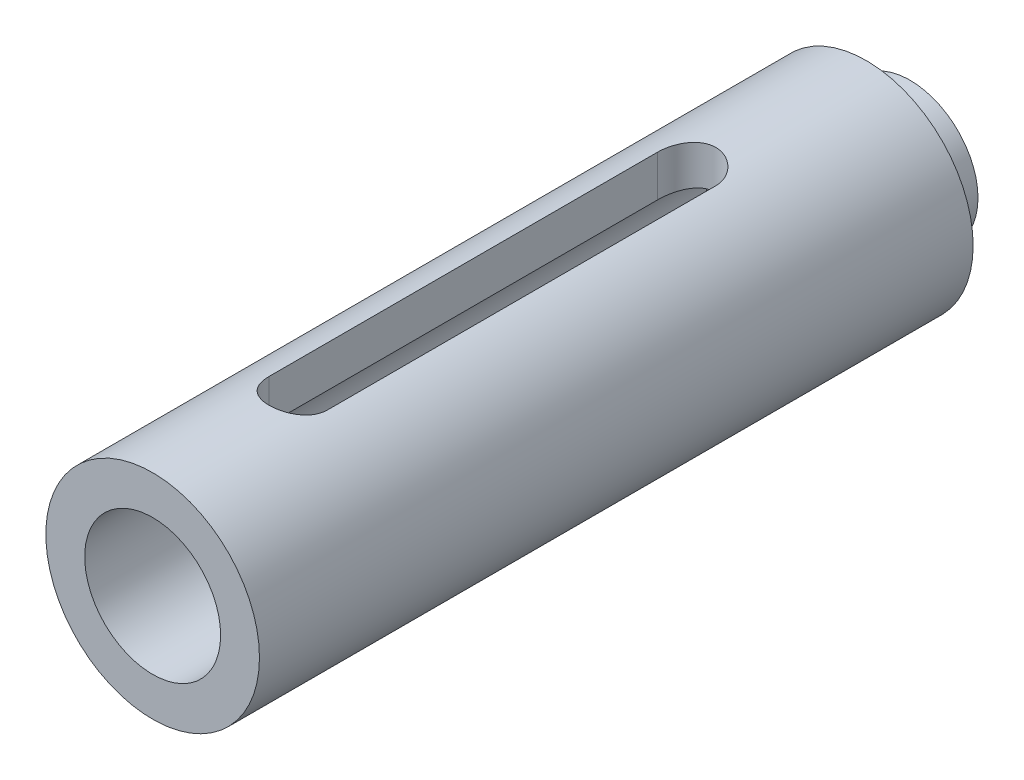
SolidWorks part; units mm, degrees
material "Zinc AC41A Alloy, As Cast"
ref_plane "Plan de face" through (0, 0, 0) normal (0, 0, 1) x (1, 0, 0)
ref_plane "Plan de dessus" through (0, 0, 0) normal (0, 1, 0) x (1, 0, 0)
ref_plane "Plan de droite" through (0, 0, 0) normal (1, 0, 0) x (0, 0, -1)
sketch "Sketch1" plane through (0, 0, 0) normal (0, 0, 1) x (1, 0, 0)
  circle A0 centre (0, 0) radius 3.5
  dimension "D1" = 7
extrude "Boss-Extrude1" add sketch "Sketch1" along normal blind 2.25
sketch "Sketch2" plane through (0, 0, 2.25) normal (0, 0, 1) x (1, 0, 0)
  circle A0 centre (0, 0) radius 5.5
  dimension "D1" = 11
extrude "Boss-Extrude2" add sketch "Sketch2" along normal blind 36.75
sketch "Sketch3" plane through (0, 0, 39) normal (0, 0, 1) x (1, 0, 0)
  circle A0 centre (0, 0) radius 3.5
  dimension "D1" = 7
extrude "Cut-Extrude1" cut sketch "Sketch3" against normal blind 33
sketch "Sketch4" plane through (0, 0, 0) normal (0, 0, -1) x (-1, 0, 0)
  circle A0 centre (0, 0) radius 2
  dimension "D1" = 4
extrude "Cut-Extrude2" cut sketch "Sketch4" against normal up to next
cosmetic thread "Cosmetic Thread1" parameters "D2"=5
chamfer "Chamfer1" distance 1 distance2 1.5 1 edges at (3.5, 0, 6) first distance on face at (3.5, 0, 6)
sketch "Sketch5" plane through (0, 0, 0) normal (0, 1, 0) x (1, 0, 0)
  line L0 (5.5, -2.25) -> (-5.5, -2.25) construction
  line L1 (-5.5, -39) -> (5.5, -39) construction
  line L2 (-1.5, -11.5) -> (-1.5, -31.5)
  line L3 (1.5, -11.5) -> (1.5, -31.5)
  arc A0 (1.5, -11.5) -> (-1.5, -11.5) centre (0, -11.5) ccw
  arc A1 (-1.5, -31.5) -> (1.5, -31.5) centre (0, -31.5) ccw
  dimension "D1" = 3
  dimension "D3" = 7.5
  dimension "D4" = 3
  dimension "D2" = 9.25
extrude "Cut-Extrude3" cut sketch "Sketch5" along normal through all
